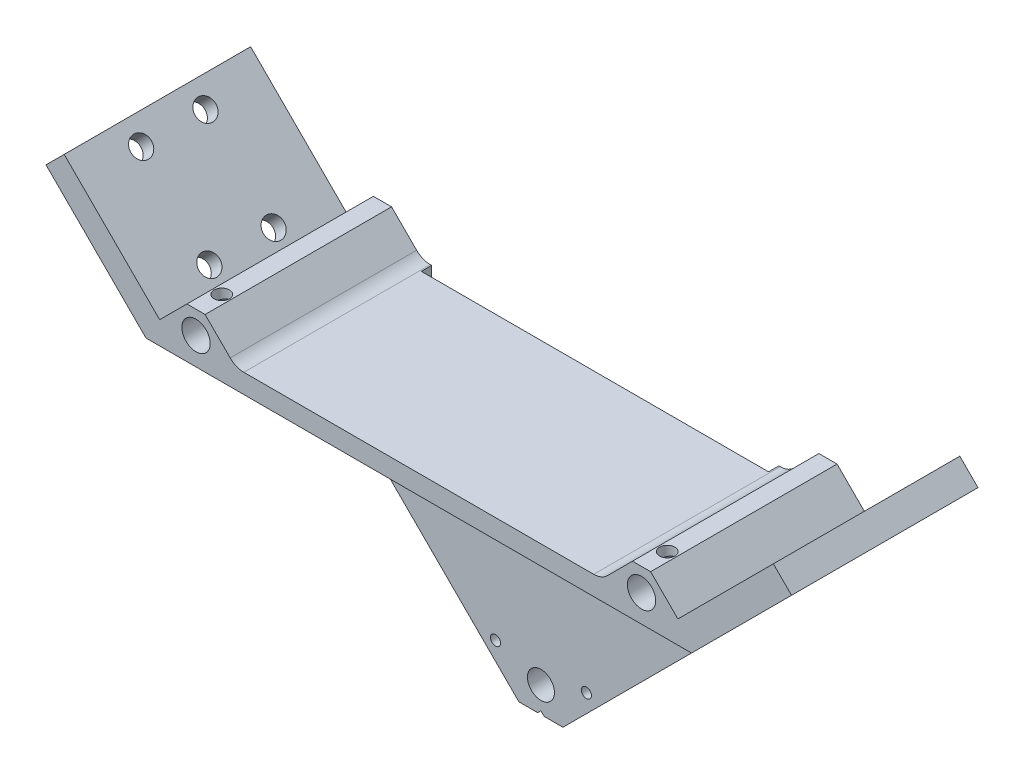
SolidWorks part; units mm, degrees
ref_plane "前视基准面" through (0, 0, 0) normal (0, 0, 1) x (1, 0, 0)
ref_plane "上视基准面" through (0, 0, 0) normal (0, 1, 0) x (1, 0, 0)
ref_plane "右视基准面" through (0, 0, 0) normal (1, 0, 0) x (0, 0, -1)
sketch "Model" plane through (0, 0, 0) normal (0, 0, 1) x (1, 0, 0)
  line L0 (454.0233, -27.1498) -> (454.0233, -18.2086)
  line L1 (453.1446, -29.2711) -> (438.0858, -44.33)
  line L2 (435.9644, -45.2086) -> (422.0822, -45.2086)
  line L3 (419.9609, -44.33) -> (404.902, -29.2711)
  line L4 (404.0233, -27.1498) -> (404.0233, -18.2086)
  line L5 (451.0233, -15.2086) -> (407.0233, -15.2086)
  line L6 (430.4964, -46.2086) -> (427.5502, -46.2086)
  line L7 (421.9522, -50.564) -> (425.4289, -47.0873)
  line L8 (425.5969, -54.2086) -> (371.0406, 0.3477)
  line L9 (397.9106, -26.5223) -> (401.1446, -23.2883)
  line L10 (402.0233, -21.167) -> (402.0233, -12.2086)
  line L11 (456.2365, -12.2086) -> (401.8101, -12.2086)
  line L12 (456.0233, -21.167) -> (456.0233, -12.2086)
  line L13 (460.136, -26.5223) -> (456.902, -23.2883)
  line L14 (432.4497, -54.2086) -> (487.0061, 0.3477)
  line L15 (436.0944, -50.564) -> (432.6177, -47.0873)
  line L16 (373.869, 3.1761) -> (371.0406, 0.3477)
  line L17 (388.7182, -11.6731) -> (373.869, 3.1761)
  line L18 (388.7182, -11.6731) -> (392.9609, -7.4305)
  line L19 (392.9609, -7.4305) -> (395.7893, -7.4305)
  line L20 (395.7893, -7.4305) -> (399.6888, -11.33)
  line L21 (462.2573, -7.4305) -> (458.3578, -11.33)
  line L22 (465.0858, -7.4305) -> (462.2573, -7.4305)
  line L23 (469.3284, -11.6731) -> (465.0858, -7.4305)
  line L24 (484.1776, 3.1761) -> (469.3284, -11.6731)
  line L25 (487.0061, 0.3477) -> (484.1776, 3.1761)
  line L26 (429.5233, -54.2086) -> (429.0233, -53.7086)
  line L27 (428.5233, -54.2086) -> (429.0233, -53.7086)
  line L28 (428.5233, -54.2086) -> (425.5969, -54.2086)
  line L29 (432.4497, -54.2086) -> (429.5233, -54.2086)
  arc A0 (454.0233, -18.2086) -> (451.0233, -15.2086) centre (451.0233, -18.2086) ccw
  arc A1 (453.1446, -29.2711) -> (454.0233, -27.1498) centre (451.0233, -27.1498) ccw
  arc A2 (435.9644, -45.2086) -> (438.0858, -44.33) centre (435.9644, -42.2086) ccw
  arc A3 (419.9609, -44.33) -> (422.0822, -45.2086) centre (422.0822, -42.2086) ccw
  arc A4 (404.0233, -27.1498) -> (404.902, -29.2711) centre (407.0233, -27.1498) ccw
  arc A5 (407.0233, -15.2086) -> (404.0233, -18.2086) centre (407.0233, -18.2086) ccw
  arc A6 (432.6177, -47.0873) -> (430.4964, -46.2086) centre (430.4964, -49.2086) ccw
  arc A7 (427.5502, -46.2086) -> (425.4289, -47.0873) centre (427.5502, -49.2086) ccw
  arc A8 (401.1446, -23.2883) -> (402.0233, -21.167) centre (399.0233, -21.167) ccw
  arc A9 (456.0233, -21.167) -> (456.902, -23.2883) centre (459.0233, -21.167) ccw
  circle A10 centre (394.3751, -10.966) radius 2.2
  arc A11 (399.6888, -11.33) -> (401.8101, -12.2086) centre (401.8101, -9.2086) ccw
  arc A12 (456.2365, -12.2086) -> (458.3578, -11.33) centre (456.2365, -9.2086) ccw
  circle A13 centre (463.6715, -10.966) radius 2.2
  circle A14 centre (429.0233, -50.2086) radius 2.1
  circle A15 centre (461.0233, -20.2086) radius 2.1
  circle A16 centre (397.0233, -20.2086) radius 2.1
  circle A17 centre (457.3076, -26.5223) radius 0.7835
  circle A18 centre (439.0233, -13.7086) radius 0.7835
  circle A19 centre (419.0233, -13.7086) radius 0.7835
  circle A20 centre (454.0233, -13.7086) radius 0.7835
  circle A21 centre (404.0233, -13.7086) radius 0.7835
  circle A22 centre (400.739, -26.5223) radius 0.7835
  circle A23 centre (436.0944, -47.7356) radius 0.7835
  circle A24 centre (421.9522, -47.7356) radius 0.7835
extrude "凸台-拉伸1" add sketch "Model" along normal blind 29 contours A11 L20 L19 L18 L17 L16 L8 L9 A8 L10 L11 A16 A10 | L5 A5 L4 A4 L3 A3 L2 A2 L1 A1 L0 A0 | A9 L12 L11 L10 A8 L9 L8 L7 A7 L6 A6 L15 L14 L13 A24 A23 A22 A21 A20 A19 A18 A17 A5 L5 A0 L0 A1 L1 A2 L2 A3 L3 A4 L4 | L6 A7 L7 L8 L28 L27 L26 L29 L14 L15 A6 A14 | A12 L11 L12 A9 L13 L14 L25 L24 L23 L22 L21 A15 A13 | A20 | A18 | A19 | A21 | A22 | A17 region at (429.0233, -28.0592, 0) region at (431.5823, -46.5871, 0) region at (429.0233, -45.4777, 0) region at (468.1108, -12.5609, 0) region at (389.9359, -12.5609, 0) region at (439.0233, -13.7086, 0) region at (419.0233, -13.7086, 0) region at (454.0233, -13.7086, 0) region at (404.0233, -13.7086, 0)
extrude "切除-拉伸1" cut sketch "Model<3>" along normal blind 1.6 contours A9 L12 L11 L10 A8 L9 L8 L7 A7 L6 A6 L15 L14 L13 A24 A23 A22 A21 A20 A19 A18 A17 A5 L5 A0 L0 A1 L1 A2 L2 A3 L3 A4 L4 | L5 A5 L4 A4 L3 A3 L2 A2 L1 A1 L0 A0 | A18 | A20 | A21 | A19 | A22 | A17 region at (429.0233, -28.0592, 0) region at (429.0233, -45.4777, 0) region at (457.3076, -26.5223, 0) region at (439.0233, -13.7086, 0) region at (419.0233, -13.7086, 0) region at (454.0233, -13.7086, 0) region at (404.0233, -13.7086, 0) region at (400.739, -26.5223, 0)
sketch "Model<3>" plane through (0, 0, 0) normal (0, 0, 1) x (1, 0, 0) same geometry as "Model"
sketch "草图2" plane through (0, 0, 29) normal (0, 0, 1) x (1, 0, 0)
  line L0 (376.1572, -15.2086) -> (485.7045, -15.2086)
  line L1 (485.7045, -15.2086) -> (432.4497, -54.2086)
  line L2 (432.4497, -54.2086) -> (404.6795, -54.2086)
  line L3 (404.6795, -54.2086) -> (376.1572, -15.2086)
  dimension "D1" = 39
extrude "切除-拉伸2" cut sketch "草图2" against normal blind 19
extrude "切除-拉伸3" cut sketch "Model<4>" along normal blind 14 contours A20 | A18 | A19 | A21 | A17 | A22 region at (457.3076, -26.5223, 0) region at (439.0233, -13.7086, 0) region at (419.0233, -13.7086, 0) region at (454.0233, -13.7086, 0) region at (404.0233, -13.7086, 0) region at (400.739, -26.5223, 0)
sketch "Model<4>" plane through (0, 0, 0) normal (0, 0, 1) x (1, 0, 0) same geometry as "Model"
extrude "切除-拉伸4" cut sketch "Model<5>" along normal blind 8.5 contours L5 A5 L4 A4 L3 A3 L2 A2 L1 A1 L0 A0 region at (429.0233, -28.0592, 0)
sketch "Model<5>" plane through (0, 0, 0) normal (0, 0, 1) x (1, 0, 0) same geometry as "Model"
sketch "草图3" plane through (185.6941, 185.6941, 0) normal (-0.7071, -0.7071, 0) x (0, 0, 1)
  line L0 (0, -300.1194) -> (0, -262.1194) construction
  line L1 (29, -284.1194) -> (29, -262.1194) construction
  line L2 (29, -262.1194) -> (0, -262.1194) construction
  circle A0 centre (9.5, -265.6194) radius 1.6
  circle A1 centre (9.5, -280.6194) radius 1.6
  circle A2 centre (19.5, -265.6194) radius 1.6
  circle A3 centre (19.5, -280.6194) radius 1.6
  dimension "D1" = 9.5
  dimension "D2" = 9.5
  dimension "D3" = 9.5
  dimension "D4" = 9.5
  dimension "D5" = 3.5
  dimension "D6" = 3.5
  dimension "D7" = 15
  dimension "D8" = 15
  dimension "D9" = 3.2
  dimension "D10" = 3.2
  dimension "D11" = 3.2
  dimension "D12" = 3.2
extrude "切除-拉伸5" cut sketch "草图3" against normal blind 20.5
ref_plane "基准面4" through (429.0233, 0, 0) normal (-1, 0, 0) x (0, 0, 1)
sketch "草图4" plane through (0, -7.4305, 0) normal (0, 1, 0) x (1, 0, 0)
  line L1 (392.9609, -29) -> (395.7893, -29) construction
  circle A0 centre (394.3751, -25) radius 1.2
  point P4 (394.3751, -29)
  dimension "D1" = 2.4
  dimension "D2" = 0
  dimension "D3" = 4
extrude "切除-拉伸6" cut sketch "草图4" against normal blind 20.5
mirror "镜向5" about plane through (429.0233, 0, 0) normal (-1, 0, 0) of "切除-拉伸6", "切除-拉伸5"
chamfer "倒角1" distance 1.65 angle 45 10 edges at (385.2534, -13.8651, 9.5) (385.2534, -13.8651, 19.5) (374.6468, -3.2585, 19.5) (374.6468, -3.2585, 9.5) (394.3751, -15.2086, 26.2) (472.7932, -13.8651, 19.5) (483.3998, -3.2585, 19.5) (483.3998, -3.2585, 9.5) (472.7932, -13.8651, 9.5) (463.6715, -15.2086, 26.2)
